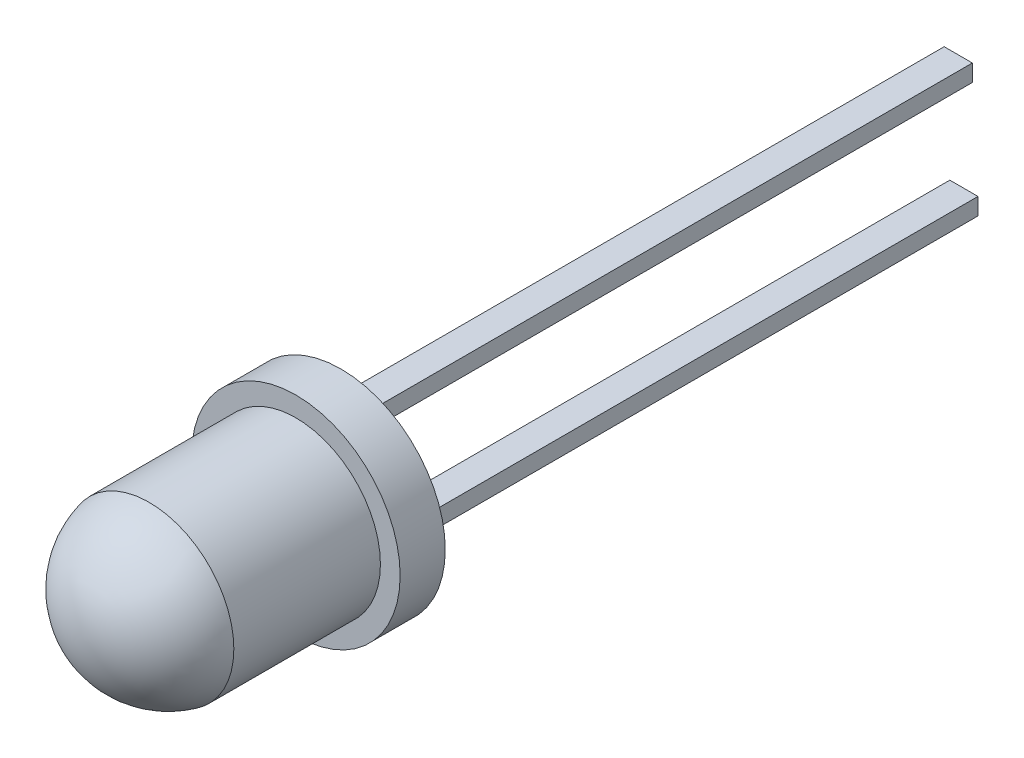
SolidWorks part; units mm, degrees
ref_plane "Front Plane" through (0, 0, 0) normal (0, 0, 1) x (1, 0, 0)
ref_plane "Top Plane" through (0, 0, 0) normal (0, 1, 0) x (1, 0, 0)
ref_plane "Right Plane" through (0, 0, 0) normal (1, 0, 0) x (0, 0, -1)
sketch "Sketch1" plane through (0, 0, 0) normal (0, 0, 1) x (1, 0, 0)
  circle A0 centre (0, 0) radius 1.5
  dimension "D1" = 3
extrude "Boss-Extrude1" add sketch "Sketch1" along normal mid plane 2.6
sketch "Sketch2" plane through (0, 0, 0) normal (0, 0, 1) x (1, 0, 0)
  circle A0 centre (0, 0) radius 1.85
  dimension "D1" = 3.7
extrude "Boss-Extrude2" add sketch "Sketch2" against normal blind 0.8 from surface starting at face at (1.5, 0, -1.3)
dome "Dome1" faces to dome 1 distance 1.2 reverse direction no elliptical dome no face at (1.5, 0, 1.3) parameters "D1"=1.2
sketch "Sketch3" plane through (0, 0, 0) normal (0, 0, 1) x (1, 0, 0)
  line L0 (0.8, 0) -> (0, 0) construction
  line L1 (1.3, 0.15) -> (0.8, 0.15)
  line L2 (1.3, 0.15) -> (1.3, -0.15)
  line L3 (1.3, -0.15) -> (0.8, -0.15)
  line L4 (0.8, 0.15) -> (0.8, -0.15)
  line L5 (-0.8, 0.15) -> (-1.3, 0.15)
  line L6 (-0.8, 0.15) -> (-0.8, -0.15)
  line L7 (-0.8, -0.15) -> (-1.3, -0.15)
  line L8 (-1.3, 0.15) -> (-1.3, -0.15)
  line L9 (0, 0) -> (-0.8, 0) construction
  point P8 (0.8, 0)
  point P9 (-0.8, 0)
  dimension "D1" = 0.5
  dimension "D2" = 0.3
  dimension "D3" = 1.6
extrude "Boss-Extrude3" add sketch "Sketch3" against normal blind 12 from surface starting at face at (1.85, 0, -2.1)
sketch "Sketch4" plane through (0, 0, 0) normal (0, 0, 1) x (1, 0, 0)
  line L1 (1.3, 0.15) -> (0.8, 0.15)
  line L2 (1.3, 0.15) -> (1.3, -0.15)
  line L3 (1.3, -0.15) -> (0.8, -0.15)
  line L4 (0.8, 0.15) -> (0.8, -0.15)
extrude "Cut-Extrude1" cut sketch "Sketch4" along normal blind 2 from surface starting at face at (1.05, 0, -14.1)
